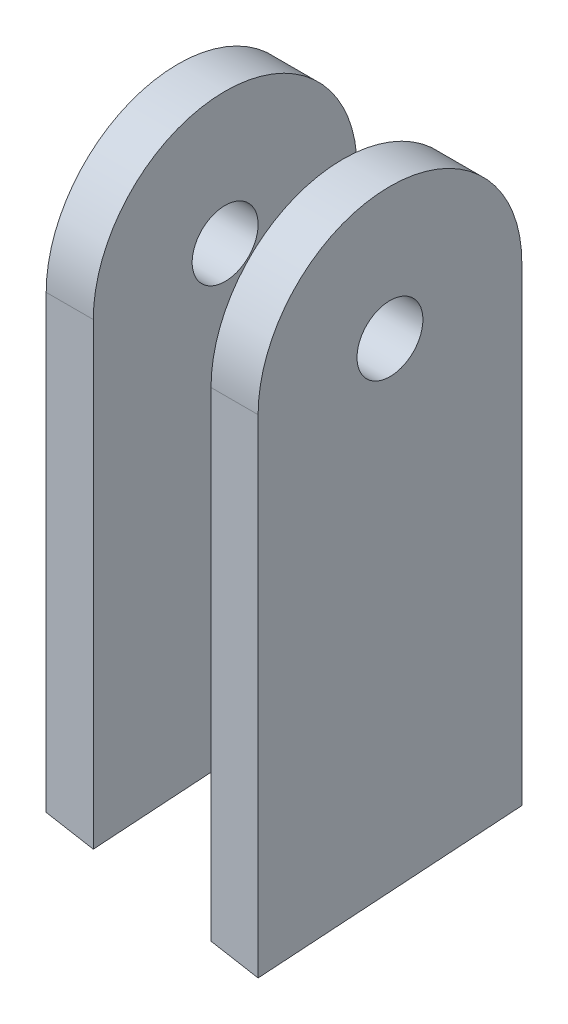
SolidWorks part; units mm, degrees
ref_plane "前视基准面" through (0, 0, 0) normal (0, 0, 1) x (1, 0, 0)
ref_plane "上视基准面" through (0, 0, 0) normal (0, 1, 0) x (1, 0, 0)
ref_plane "右视基准面" through (0, 0, 0) normal (1, 0, 0) x (0, 0, -1)
sketch "草图1" plane through (0, 0, 0) normal (1, 0, 0) x (0, 0, -1)
  line L0 (-28, 0) -> (-28, -200)
  line L1 (28, 0) -> (28, -200)
  line L2 (28, -200) -> (-28, -200)
  arc A0 (28, 0) -> (-28, 0) centre (0, 0) ccw
  circle A1 centre (0, 0) radius 7
extrude "凸台-拉伸1" add sketch "草图1" along normal blind 10 and the other way blind 35
extrude "切除-拉伸1" cut sketch "草图1<2>" against normal blind 25
sketch "草图1<2>" plane through (0, 0, 0) normal (1, 0, 0) x (0, 0, -1) same geometry as "草图1"
sketch "草图2" plane through (-17.06, -96.5419, -6.3762) normal (0.1736, 0.9827, 0.0649) x (-0.9498, 0.1845, -0.2525)
  circle A0 centre (0, 0) radius 162.6221
extrude "切除-拉伸2" cut sketch "草图2" against normal blind 168
